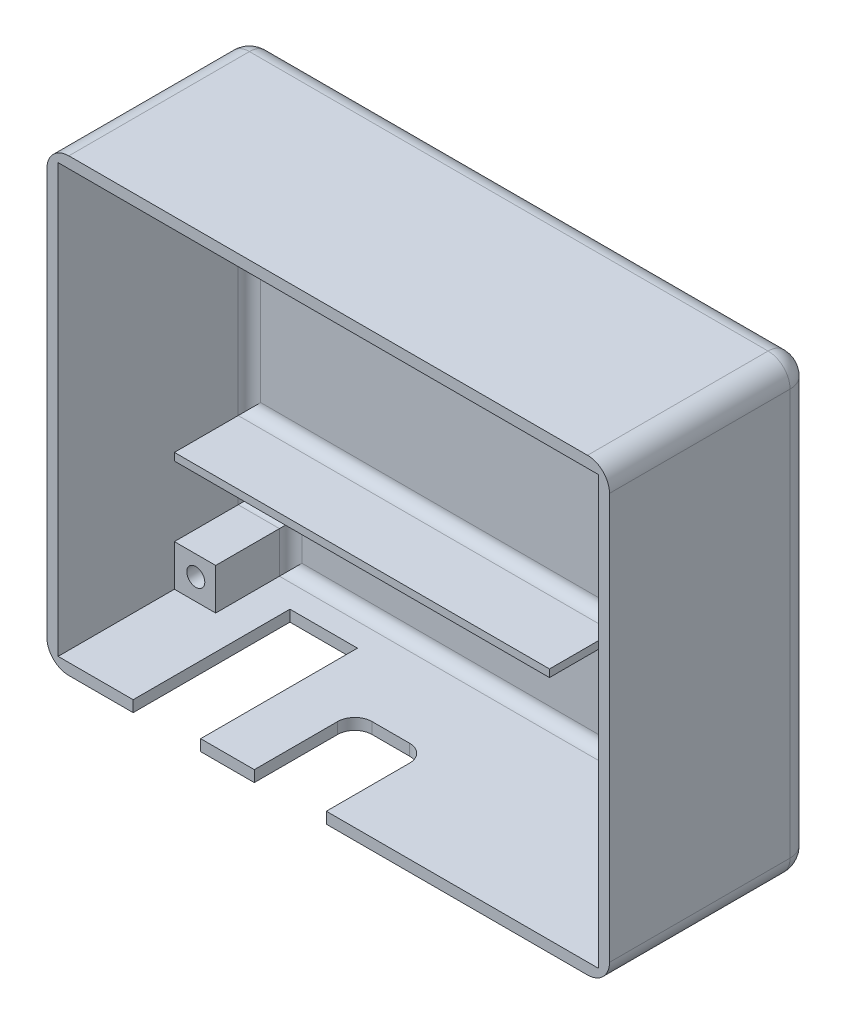
SolidWorks part; units mm, degrees
ref_plane "Front Plane" through (0, 0, 0) normal (0, 0, 1) x (1, 0, 0)
ref_plane "Top Plane" through (0, 0, 0) normal (0, 1, 0) x (1, 0, 0)
ref_plane "Right Plane" through (0, 0, 0) normal (1, 0, 0) x (0, 0, -1)
sketch "Sketch2" plane through (0, 0, 0) normal (0, 0, 1) x (1, 0, 0)
  line L1 (0, 0) -> (75, 0)
  line L2 (0, 0) -> (0, 60)
  line L3 (0, 60) -> (75, 60)
  line L4 (75, 0) -> (75, 60)
  dimension "D1" = 75
  dimension "D2" = 60
extrude "Body creation" add sketch "Sketch2" along normal blind 27
shell "Thikness of walls" thickness 1.5 removed face at (37.5, 30, 27)
ref_plane "Plane1" through (0, 30, 0) normal (0, -1, 0) x (-1, 0, 0)
sketch "Sketch6" plane through (0, 0, 1.5) normal (0, 0, 1) x (1, 0, 0)
  line L1 (1.5, 58.5) -> (7, 58.5)
  line L2 (1.5, 58.5) -> (1.5, 53)
  line L3 (1.5, 53) -> (7, 53)
  line L4 (7, 58.5) -> (7, 53)
  line L5 (73.5, 58.5) -> (68, 58.5)
  line L6 (73.5, 58.5) -> (73.5, 53)
  line L7 (73.5, 53) -> (68, 53)
  line L8 (68, 58.5) -> (68, 53)
  dimension "D1" = 5.5
extrude "Corner rect." add sketch "Sketch6" along normal blind 10
sketch "Sketch8" plane through (0, 0, 27) normal (0, 0, 1) x (1, 0, 0)
  line L0 (4.35, 55.65) -> (4.35, 53) construction
  line L1 (1.5, 53) -> (7, 53) construction
  line L2 (7, 55.65) -> (4.35, 55.65) construction
  line L3 (7, 53) -> (7, 58.5) construction
  line L4 (68, 55.65) -> (70.65, 55.65) construction
  line L7 (70.65, 55.65) -> (70.65, 53) construction
  line L9 (68, 58.5) -> (68, 53) construction
  line L10 (68, 53) -> (73.5, 53) construction
  circle A0 centre (4.35, 55.65) radius 1.2
  circle A1 centre (70.65, 55.65) radius 1.2
  dimension "D1" = 2.4
  dimension "D2" = 2.65
  dimension "D3" = 2.65
extrude "Screw hole" cut sketch "Sketch8" against normal up to surface (27 mm away) up to face at (37.5, 30, 0)
sketch "Sketch10" plane through (0, 0, 0) normal (0, 0, -1) x (-1, 0, 0)
  circle A0 centre (-70.65, 55.65) radius 2
  circle A1 centre (-4.35, 55.65) radius 2
  dimension "D1" = 4
extrude "Screw head" cut sketch "Sketch10" against normal blind 4
mirror "Mirror to other side" about plane through (0, 30, 0) normal (0, -1, 0) of "Screw head", "Corner rect.", "Screw hole"
sketch "Sketch5" plane through (0, 0, 0) normal (0, -1, 0) x (1, 0, 0)
  line L0 (32.45, 15.9) -> (32.45, 27) construction
  line L1 (20.5, 27) -> (11.5, 27)
  line L2 (20.5, 27) -> (20.5, 6.1)
  line L3 (20.5, 6.1) -> (11.5, 6.1)
  line L4 (11.5, 27) -> (11.5, 6.1)
  line L5 (0, 27) -> (0, 0) construction
  line L6 (29.95, 15.9) -> (34.95, 15.9) construction
  line L7 (16, 27) -> (16, 6.1) construction
  line L8 (0, 0) -> (75, 0) construction
  line L10 (29.95, 13.6) -> (34.95, 13.6)
  line L13 (27.65, 15.9) -> (27.65, 27)
  line L14 (37.25, 15.9) -> (37.25, 27)
  line L15 (27.65, 27) -> (37.25, 27)
  line L16 (0, 27) -> (75, 27) construction
  arc A0 (27.65, 15.9) -> (29.95, 13.6) centre (29.95, 15.9) ccw
  arc A1 (34.95, 13.6) -> (37.25, 15.9) centre (34.95, 15.9) ccw
  dimension "D6" = 13.6
  dimension "D8" = 2.3
  dimension "D1" = 6.1
  dimension "D2" = 9
  dimension "D3" = 2.3
  dimension "D4" = 16
  dimension "D5" = 5
  dimension "D7" = 11.95
extrude "Ports cut out" cut sketch "Sketch5" against normal up to surface (1.5 mm away) up to face at (37.5, 1.5, 12.875)
sketch "Sketch11" plane through (0, 0, 1.5) normal (0, 0, 1) x (1, 0, 0)
  line L0 (1.5, 53) -> (1.5, 7) construction
  line L1 (7, 53) -> (51.5, 53)
  line L3 (1.5, 17.3) -> (51.5, 17.3)
  line L5 (7, 54) -> (51.5, 54)
  line L6 (1.5, 16.3) -> (51.5, 16.3)
  line L7 (51.5, 17.3) -> (51.5, 16.3)
  line L8 (51.5, 54) -> (51.5, 53)
  line L9 (7, 54) -> (7, 53)
  line L10 (1.5, 17.3) -> (1.5, 16.3)
  line L11 (1.5, 58.5) -> (1.5, 1.5) construction
  line L12 (68, 58.5) -> (66.75, 58.5)
  line L13 (68, 58.5) -> (68, 36)
  line L14 (68, 36) -> (66.75, 36)
  line L15 (66.75, 58.5) -> (66.75, 36)
  line L16 (68, 58.5) -> (68, 53) construction
  line L18 (68, 58.5) -> (7, 58.5) construction
  dimension "D1" = 35.7
  dimension "D2" = 50
  dimension "D5" = 65.25
  dimension "D6" = 22.5
  dimension "D3" = 1
  dimension "D4" = 1
extrude "Battery Placement" add sketch "Sketch11" along normal blind 10
fillet "Fillet1" radius 1.5 20 edges at (1.5, 11.65, 1.5) (7, 56.25, 1.5) (29.25, 54, 1.5) (26.5, 16.3, 1.5) (1.5, 35.15, 1.5) (26.5, 53, 1.5) (51.5, 53.5, 1.5) (36.875, 58.5, 1.5) (70.75, 53, 1.5) (73.5, 30, 1.5) (70.75, 7, 1.5) (68, 4.25, 1.5) (37.5, 1.5, 1.5) (7, 4.25, 1.5) (4.25, 7, 1.5) (51.5, 16.8, 1.5) (26.5, 17.3, 1.5) (66.75, 47.25, 1.5) (67.375, 36, 1.5) (68, 44.5, 1.5)
fillet "Fillet2" radius 2.93 8 edges at (0, 60, 13.5) (75, 60, 13.5) (75, 0, 13.5) (0, 0, 13.5) (37.5, 60, 0) (75, 30, 0) (37.5, 0, 0) (0, 30, 0)
sketch "Sketch13" plane through (0, 0, 0) normal (0, 0, -1) x (-1, 0, 0)
  line L0 (-37.5, 50) -> (-37.5, 57.07) construction
  line L1 (-62.5, 50) -> (-12.5, 50)
  line L2 (-62.5, 50) -> (-62.5, 10)
  line L3 (-62.5, 10) -> (-12.5, 10)
  line L4 (-12.5, 50) -> (-12.5, 10)
  line L5 (-5.7584, 57.07) -> (-69.2416, 57.07) construction
  line L6 (-62.5, 30) -> (-72.07, 30) construction
  line L7 (-72.07, 54.2416) -> (-72.07, 5.7584) construction
  dimension "D1" = 50
  dimension "D2" = 40
extrude "Cut-Extrude1" cut sketch "Sketch13" against normal blind 1
